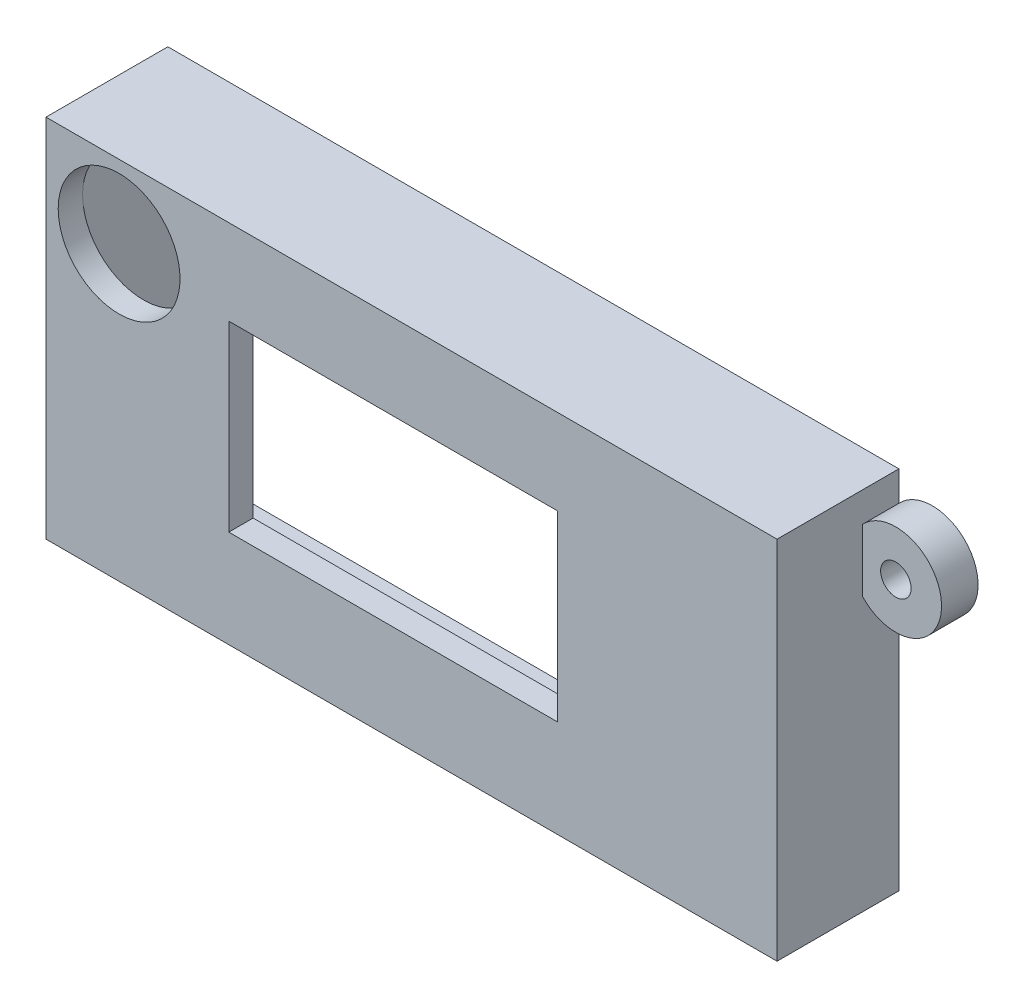
SolidWorks part; units mm, degrees
ref_plane "Ebene vorne" through (0, 0, 0) normal (0, 0, 1) x (1, 0, 0)
ref_plane "Ebene oben" through (0, 0, 0) normal (0, 1, 0) x (1, 0, 0)
ref_plane "Ebene rechts" through (0, 0, 0) normal (1, 0, 0) x (0, 0, -1)
sketch "Skizze1" plane through (0, 0, 0) normal (0, 0, 1) x (1, 0, 0)
  line L1 (-30, 15) -> (30, 15)
  line L2 (-30, 15) -> (-30, -15)
  line L3 (-30, -15) -> (30, -15)
  line L4 (30, 15) -> (30, -15)
  line L5 (-30, 15) -> (30, -15) construction
  line L6 (-30, -15) -> (30, 15) construction
  point P0 (0, 0)
  point P6 (0, 0)
  dimension "D1" = 60
  dimension "D2" = 30
extrude "Aufsatz-Linear austragen1" add sketch "Skizze1" along normal blind 10
sketch "Skizze2" plane through (0, 0, 0) normal (0, 0, -1) x (-1, 0, 0)
  line L0 (30, 15) -> (30, -15) construction
  line L1 (-12, 8) -> (15, 8)
  line L2 (-12, 8) -> (-12, -7)
  line L3 (-12, -7) -> (15, -7)
  line L4 (15, 8) -> (15, -7)
  line L5 (-12, 8) -> (15, -7) construction
  line L6 (-12, -7) -> (15, 8) construction
  line L7 (30, -15) -> (-30, -15) construction
  line L10 (-30, 15) -> (30, 15) construction
  circle A0 centre (24, 9) radius 5
  point P0 (1.5, 0.5)
  dimension "D8" = 10
  dimension "D1" = 28.5
  dimension "D2" = 27
  dimension "D3" = 15
  dimension "D4" = 15.5
  dimension "D5" = 14.5
  dimension "D6" = 15
  dimension "D7" = 9
extrude "Schnitt-Linear austragen2" cut sketch "Skizze2" against normal through all
sketch "Skizze3" plane through (0, 0, 0) normal (0, 0, -1) x (-1, 0, 0)
  line L0 (-30, 12.5495) -> (-30, 7.4505)
  line L1 (15, -7) -> (15, 8) construction
  line L2 (30, 15) -> (30, -15) construction
  line L11 (29, -14) -> (-29, -14)
  line L12 (29, -14) -> (29, 14)
  line L13 (29, 14) -> (-29, 14)
  line L14 (-29, -14) -> (-29, 14)
  line L15 (29, -14) -> (-29, 14) construction
  line L16 (29, 14) -> (-29, -14) construction
  line L17 (30, -8.0539) -> (30, -11.9461)
  line L18 (30, -15) -> (-30, -15) construction
  line L19 (-30, -15) -> (-30, 15) construction
  line L20 (-30, 15) -> (30, 15) construction
  arc A6 (-30, 12.5495) -> (-30, 7.4505) centre (-32.75, 10) ccw
  circle A7 centre (-32.75, 10) radius 1.25
  circle A11 centre (33.0589, -10) radius 1.25
  arc A12 (30, -8.0539) -> (30, -11.9461) centre (33.0589, -10) cw
  point P0 (0.0703, -0.0199)
  point P2 (0, 0)
  point P23 (0, 0)
  line M6 (-30, 15) -> (-30, -15)
  dimension "D1" = 58
  dimension "D3" = 15
  dimension "D6" = 2.75
  dimension "D4" = 2.5
  dimension "D5" = 7.5
  dimension "D7" = 2.5
  dimension "D8" = 5
  dimension "D9" = 5
  dimension "D2" = 28
extrude "Schnitt-Linear austragen3" cut sketch "Skizze3" against normal blind 8
extrude "Aufsatz-Linear austragen3" add sketch "Skizze3<4>" against normal blind 3
sketch "Skizze3<4>" plane through (0, 0, 0) normal (0, 0, -1) x (-1, 0, 0) same geometry as "Skizze3"
extrude "Schnitt-Linear austragen7" cut sketch "Skizze3<5>" against normal blind 3
sketch "Skizze3<5>" plane through (0, 0, 0) normal (0, 0, -1) x (-1, 0, 0) same geometry as "Skizze3"
extrude "Aufsatz-Linear austragen4" add sketch "Skizze3<7>" against normal blind 3 contours A6 A7 M6 region at (30.0992, 10, 0)
sketch "Skizze3<7>" plane through (0, 0, 0) normal (0, 0, -1) x (-1, 0, 0) same geometry as "Skizze3"
extrude "Aufsatz-Linear austragen5" add sketch "Skizze3<9>" against normal blind 3 separate body contours A12 L17
sketch "Skizze3<9>" plane through (0, 0, 0) normal (0, 0, -1) x (-1, 0, 0) same geometry as "Skizze3"
extrude "Schnitt-Linear austragen9" cut sketch "Skizze3<11>" against normal through all contours A11
sketch "Skizze3<11>" plane through (0, 0, 0) normal (0, 0, -1) x (-1, 0, 0) same geometry as "Skizze3"
